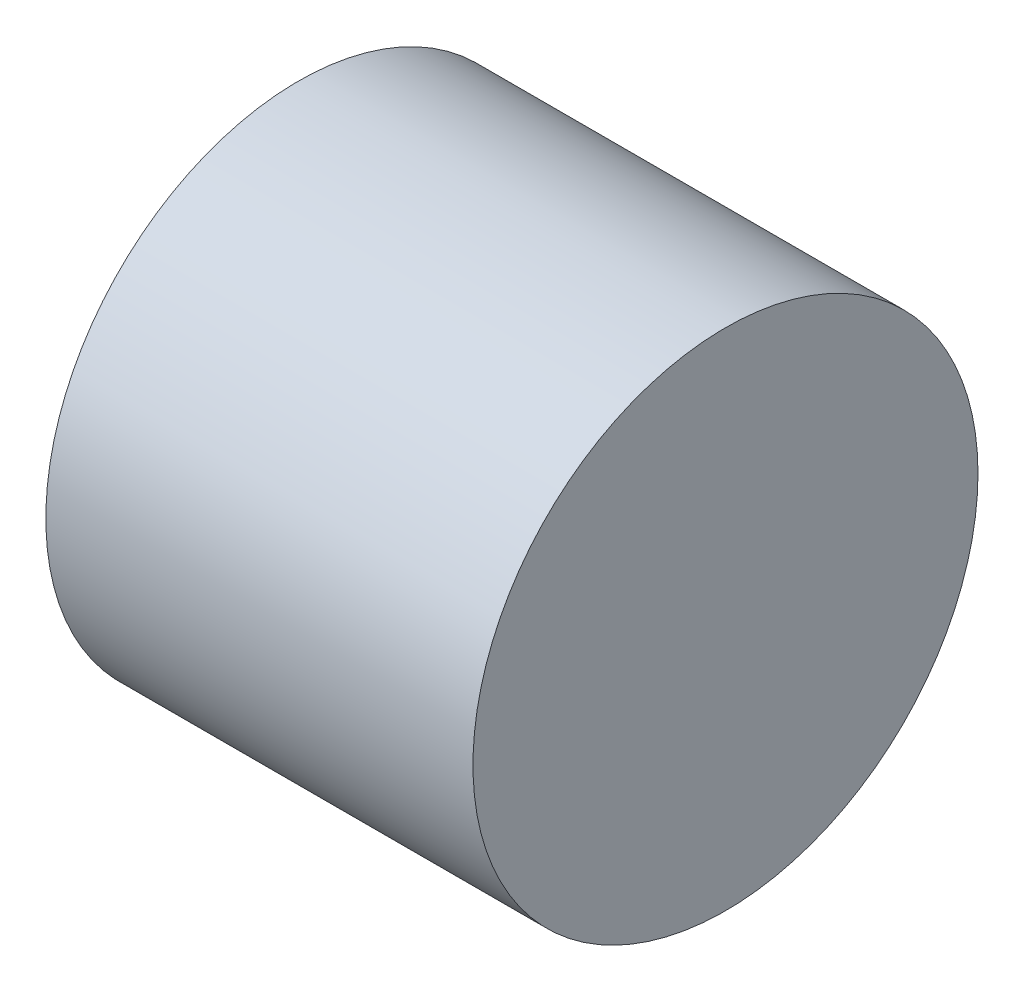
SolidWorks part; units mm, degrees
ref_plane "Front Plane" through (0, 0, 0) normal (0, 0, 1) x (1, 0, 0)
ref_plane "Top Plane" through (0, 0, 0) normal (0, 1, 0) x (1, 0, 0)
ref_plane "Right Plane" through (0, 0, 0) normal (1, 0, 0) x (0, 0, -1)
sketch "Sketch1" plane through (0, 0, 0) normal (0, 1, 0) x (1, 0, 0)
  line L0 (0, 0) -> (0, -270.5165) construction
  line L1 (-85.5216, -73.9215) -> (85.5216, -73.9215) construction
  point P6 (0, -73.9215)
sketch "Sketch2" plane through (0, 0, 0) normal (1, 0, 0) x (0, 0, -1)
  circle A0 centre (-2.5, 0) radius 17.5
  dimension "D1" = 35
extrude "Boss-Extrude1" add sketch "Sketch2" along normal blind 14.8 and the other way blind 14.8
